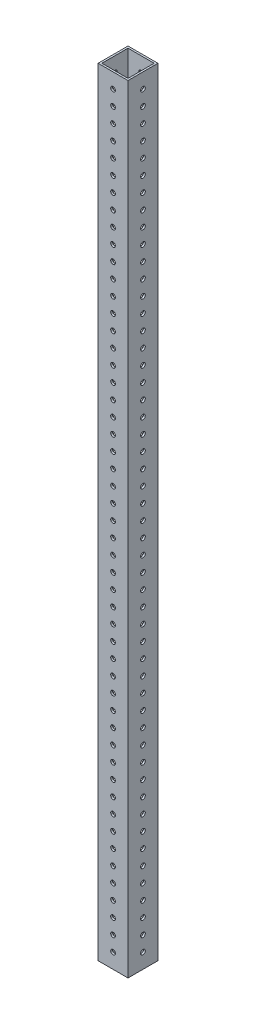
SolidWorks part; units mm, degrees
material "6061-T6 (SS)"
ref_plane "Front Plane" through (0, 0, 0) normal (0, 0, 1) x (1, 0, 0)
ref_plane "Top Plane" through (0, 0, 0) normal (0, 1, 0) x (1, 0, 0)
ref_plane "Right Plane" through (0, 0, 0) normal (1, 0, 0) x (0, 0, -1)
sketch "Sketch1" plane through (0, 0, 0) normal (0, 1, 0) x (1, 0, 0)
  line L0 (-11.1125, -11.1125) -> (-11.1125, 11.1125)
  line L1 (-12.7, -12.7) -> (12.7, -12.7)
  line L2 (-12.7, -12.7) -> (-12.7, 12.7)
  line L3 (-12.7, 12.7) -> (12.7, 12.7)
  line L4 (12.7, -12.7) -> (12.7, 12.7)
  line L5 (-12.7, -12.7) -> (12.7, 12.7) construction
  line L6 (-12.7, 12.7) -> (12.7, -12.7) construction
  line L7 (-11.1125, 11.1125) -> (11.1125, 11.1125)
  line L8 (11.1125, -11.1125) -> (11.1125, 11.1125)
  line L9 (-11.1125, -11.1125) -> (11.1125, -11.1125)
  point P0 (0, 0)
  dimension "D1" = 25.4
  dimension "D2" = 25.4
  dimension "D3" = 1.5875
extrude "Boss-Extrude1" add sketch "Sketch1" along normal blind 660.4
hole_wizard "#22 (0.157) Diameter Hole1" positions "Sketch2" profile "Sketch3" hole size "#22" standard "ANSI Inch" end condition through all
sketch "Sketch2" plane through (0, 0, 12.7) normal (0, 0, 1) x (1, 0, 0)
  line L0 (12.7, 660.4) -> (12.7, 0) construction
  line L1 (-12.7, 0) -> (12.7, 0) construction
  point P0 (0, 12.7)
  dimension "D1" = 12.7
  dimension "D2" = 12.7
sketch "Sketch3" plane through (0, 12.7, 12.7) normal (1, 0, 0) x (0, -1, 0)
  line L0 (0, 0) -> (0, 25.4)
  line L1 (0, 25.4) -> (1.9939, 25.4)
  line L2 (1.9939, 25.4) -> (1.9939, 0)
  line L5 (1.9939, 0) -> (0, 0)
  line L11 (0, -6.35) -> (0, 107.95) construction
  dimension "Thru Hole Dia." = 3.9878
  dimension "Thru Hole Depth" = 25.4
pattern_linear "LPattern1" count 51 spacing 12.7 along (0, 1, 0) of "#22 (0.157) Diameter Hole1"
hole_wizard "#22 (0.157) Diameter Hole2" positions "Sketch4" profile "Sketch5" hole size "#22" standard "ANSI Inch" end condition through all
sketch "Sketch4" plane through (12.7, 0, 0) normal (1, 0, 0) x (0, 0, -1)
  line L2 (-12.7, 660.4) -> (-12.7, 0) construction
  line L3 (-12.7, 0) -> (12.7, 0) construction
  point P0 (0, 12.7)
  dimension "D1" = 12.7
  dimension "D2" = 12.7
sketch "Sketch5" plane through (12.7, 12.7, 0) normal (0, 1, 0) x (0, 0, -1)
  line L0 (0, 0) -> (0, 25.4)
  line L1 (0, 25.4) -> (1.9939, 25.4)
  line L2 (1.9939, 25.4) -> (1.9939, 0)
  line L5 (1.9939, 0) -> (0, 0)
  line L11 (0, -6.35) -> (0, 107.95) construction
  dimension "Thru Hole Dia." = 3.9878
  dimension "Thru Hole Depth" = 25.4
pattern_linear "LPattern2" count 51 spacing 12.7 along (0, 1, 0) of "#22 (0.157) Diameter Hole2"
